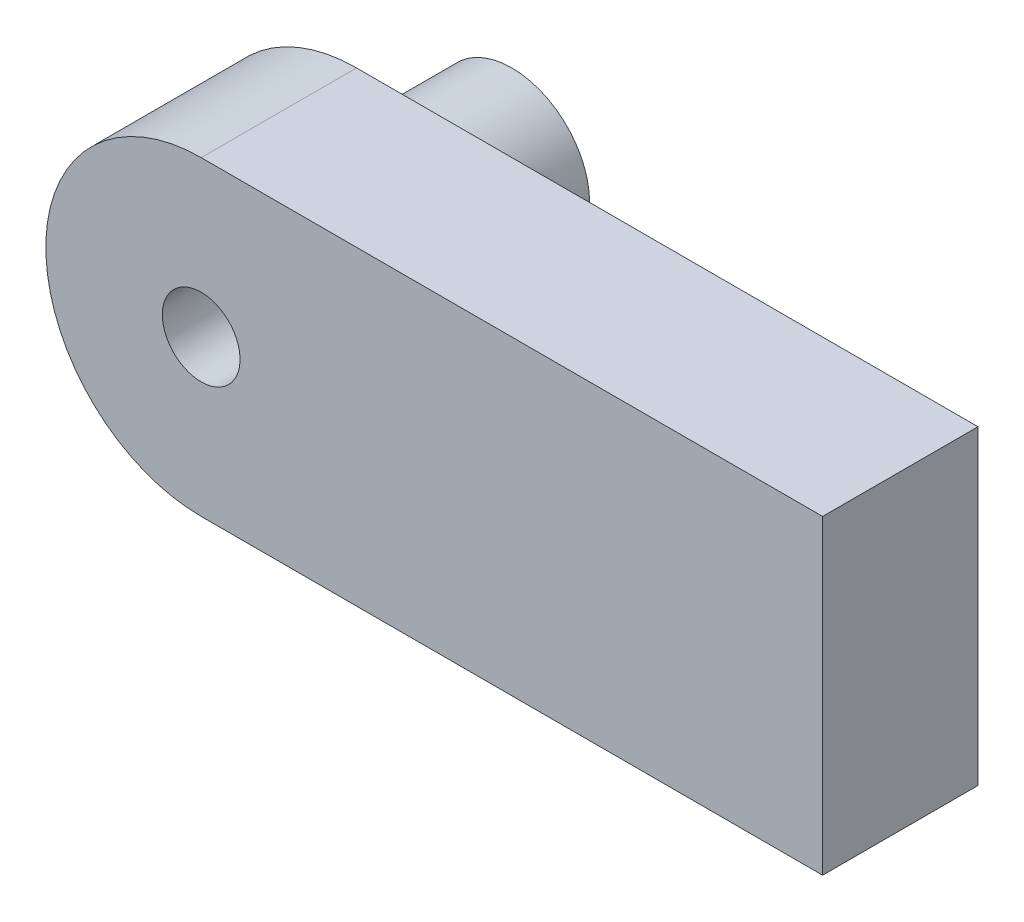
SolidWorks part; units mm, degrees
ref_plane "Piano frontale" through (0, 0, 0) normal (0, 0, 1) x (1, 0, 0)
ref_plane "Piano superiore" through (0, 0, 0) normal (0, 1, 0) x (1, 0, 0)
ref_plane "Piano destro" through (0, 0, 0) normal (1, 0, 0) x (0, 0, -1)
sketch "Schizzo1" plane through (0, 0, 0) normal (0, 0, 1) x (1, 0, 0)
  line L0 (0, 4.5035) -> (-20, 4.5035)
  line L2 (-20, -5.4965) -> (0, -5.4965)
  line L12 (0, 4.5035) -> (0, -5.4965)
  arc A0 (-20, 4.5035) -> (-20, -5.4965) centre (-20, -0.4965) ccw
  dimension "D1" = 10
  dimension "D9" = 20
extrude "Estrusione-Estrusione1" add sketch "Schizzo1" along normal blind 5
sketch "Schizzo2" plane through (0, 0, 0) normal (0, 0, -1) x (-1, 0, 0)
  arc A0 (20, -5.4965) -> (20, 4.5035) centre (20, -0.4965) ccw construction
  arc A1 (20, -5.4965) -> (20, 4.5035) centre (20, -0.4965) ccw construction
  circle A2 centre (20, -0.4965) radius 2.5
extrude "Estrusione-Estrusione2" add sketch "Schizzo2" along normal blind 5 contours A2
sketch "Schizzo3" plane through (0, 0, -5) normal (0, 0, -1) x (-1, 0, 0)
  circle A0 centre (20, -0.4965) radius 1.25
  dimension "D1" = 2.5
extrude "Taglio-Estrusione1" cut sketch "Schizzo3" against normal through all
ref_point "Punto1"
ref_axis "Assi1" through (-20, -0.4965, 5) along (0, 0, -1)
ref_axis "Assi2" through (0, 4.5035, 0) along (-1, 0, 0)
